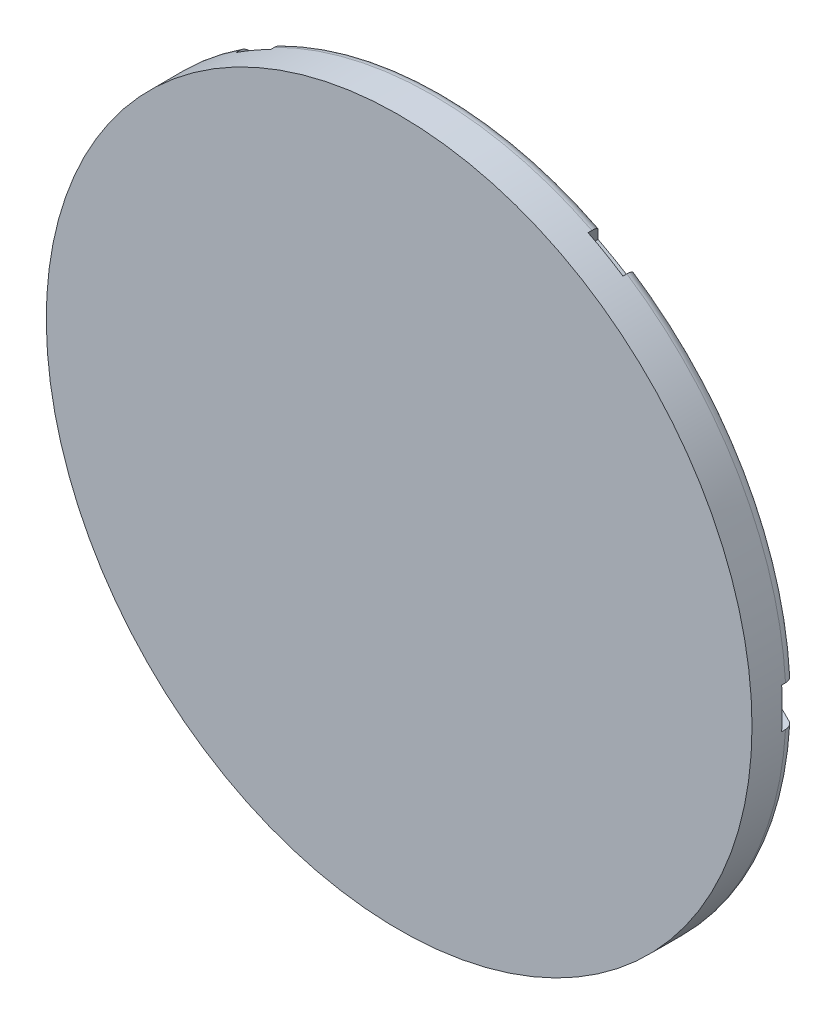
SolidWorks part; units mm, degrees
ref_plane "Front" through (0, 0, 0) normal (0, 0, 1) x (1, 0, 0)
ref_plane "Top" through (0, 0, 0) normal (0, 1, 0) x (1, 0, 0)
ref_plane "Right" through (0, 0, 0) normal (1, 0, 0) x (0, 0, -1)
sketch "Sketch1" plane through (0, 0, 0) normal (0, 0, 1) x (1, 0, 0)
  circle A0 centre (0, 0) radius 17.5
  dimension "D1" = 35
extrude "Base-Extrude" add sketch "Sketch1" along normal blind 2
chamfer "Chamfer1" distance 2 distance2 1 1 edges at (17.5, 0, 0) first distance on face at (17.5, 0, 0)
fillet "Fillet8" radius 0.5 2 edges at (17.5, 0, 1) (15.5, 0, 0)
sketch "Sketch2" plane through (0, 0, 0) normal (0, 0, -1) x (-1, 0, 0)
  line L0 (-53.4466, 0) -> (62.2609, 0) construction
  line L1 (0, 53.8727) -> (0, -50.6863) construction
  line L3 (16, 1) -> (20, 1)
  line L4 (16, 1) -> (16, -1)
  line L5 (16, -1) -> (20, -1)
  line L6 (20, 1) -> (20, -1)
  circle A0 centre (0, 0) radius 17.5 construction
  circle A1 centre (0, 0) radius 17.5 construction
  point P11 (16, 0)
  dimension "D1" = 16
  dimension "D2" = 20
  dimension "D3" = 2
extrude "Cut-Extrude1" cut sketch "Sketch2" against normal blind 1.5
pattern_circular "CirPattern1" count 6 over 360 of "Cut-Extrude1"
sketch "Sketch3" plane through (0, 0, 2) normal (0, 0, 1) x (1, 0, 0)
  circle A1 centre (0, 0) radius 17.5
  circle A2 centre (0, 0) radius 17.5
  dimension "D1" = 0
extrude "Boss-Extrude1" add sketch "Sketch3" along normal blind 1
